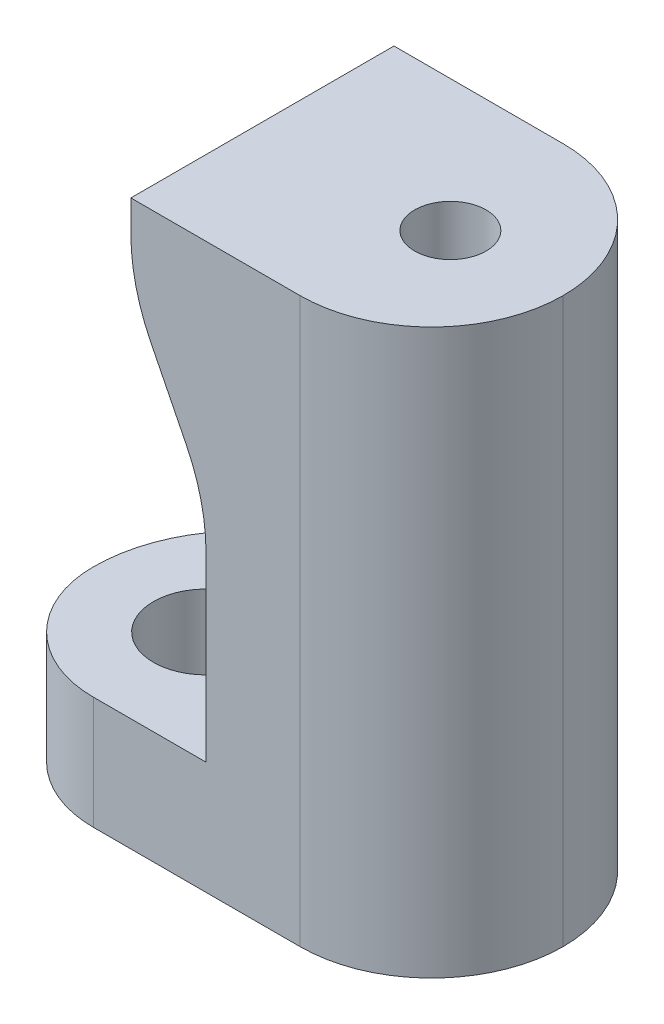
SolidWorks part; units mm, degrees
ref_plane "Plan de face" through (0, 0, 0) normal (0, 0, 1) x (1, 0, 0)
ref_plane "Plan de dessus" through (0, 0, 0) normal (0, 1, 0) x (1, 0, 0)
ref_plane "Plan de droite" through (0, 0, 0) normal (1, 0, 0) x (0, 0, -1)
sketch "Esquisse1" plane through (0, 0, 0) normal (0, 0, 1) x (1, 0, 0)
  line L0 (-2, 13) -> (0, 9)
  line L1 (0, 0) -> (-6, 0)
  line L2 (6, 15) -> (-2, 15)
  line L3 (0, 3) -> (-6, 3)
  line L4 (-6, 0) -> (-6, 3)
  line L5 (0, 0) -> (6, 0)
  line L6 (0, 3) -> (0, 9)
  line L8 (6, 0) -> (6, 15)
  line L12 (-2, 15) -> (-2, 13)
  dimension "D1" = 6
  dimension "D2" = 8
  dimension "D3" = 15
  dimension "D4" = 2
  dimension "D5" = 6
  dimension "D6" = 6
  dimension "D7" = 3
  dimension "D8" = 2
extrude "Boss.-Extru.1" add sketch "Esquisse1" along normal blind 7
sketch "Esquisse2" plane through (0, 3, 0) normal (0, 1, 0) x (1, 0, 0)
  line L1 (0, 0) -> (-6, 0) construction
  line L2 (-6, -7) -> (-6, 0) construction
  circle A0 centre (-3, -4) radius 1.4
  dimension "D1" = 2.8
  dimension "D2" = 4
  dimension "D3" = 3
extrude "Enlèv. mat.-Extru.1" cut sketch "Esquisse2" against normal through all
sketch "Esquisse3" plane through (0, 15, 0) normal (0, 1, 0) x (1, 0, 0)
  line L0 (6, 0) -> (-2, 0) construction
  line L1 (6, -7) -> (6, 0) construction
  circle A0 centre (3, -3.5) radius 0.95
  dimension "D1" = 1.9
  dimension "D2" = 3
  dimension "D3" = 3.5
extrude "Enlèv. mat.-Extru.2" cut sketch "Esquisse3" against normal blind 10
fillet "Congé1" radius 4 1 edges at (-6, 1.5, 0)
fillet "Congé2" radius 3 1 edges at (-6, 1.5, 7)
fillet "Congé3" radius 3.5 2 edges at (6, 7.5, 7) (6, 7.5, 0)
fillet "Congé4" radius 5 2 edges at (-2, 13, 3.5) (0, 9, 3.5)
